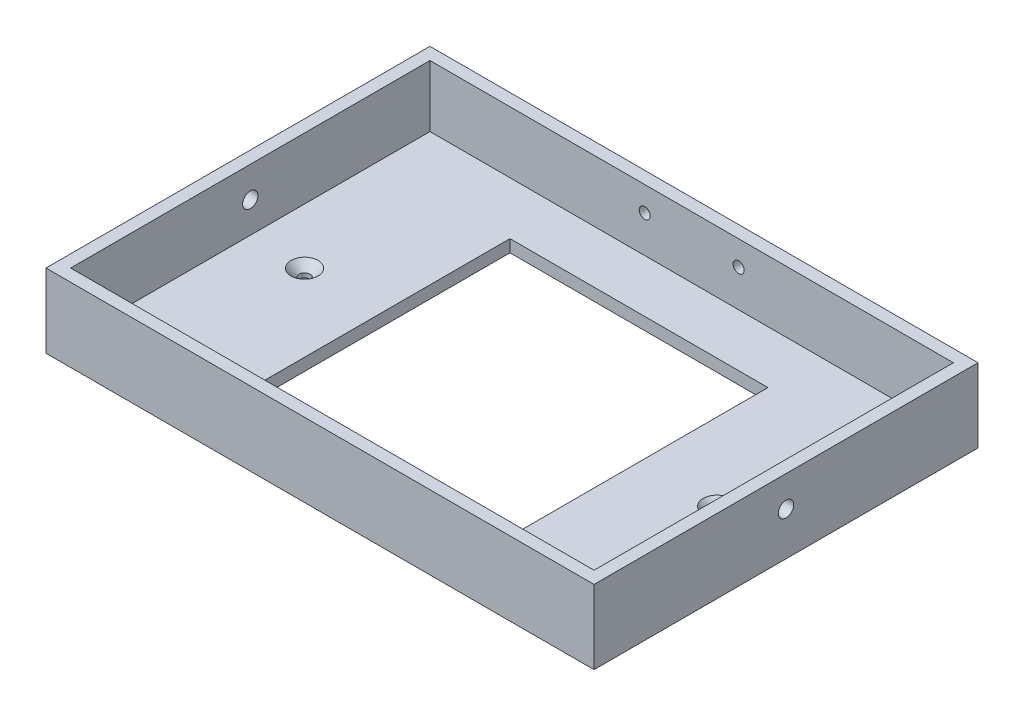
SolidWorks part; units mm, degrees
material "[PLA] Orange"
ref_plane "Front Plane" through (0, 0, 0) normal (0, 0, 1) x (1, 0, 0)
ref_plane "Top Plane" through (0, 0, 0) normal (0, 1, 0) x (1, 0, 0)
ref_plane "Right Plane" through (0, 0, 0) normal (1, 0, 0) x (0, 0, -1)
sketch "Sketch1" plane through (0, 0, 0) normal (0, 1, 0) x (1, 0, 0)
  line L0 (-44.545, -31.21) -> (-44.545, 31.21)
  line L1 (-42.545, -29.21) -> (42.545, -29.21)
  line L2 (-42.545, -29.21) -> (-42.545, 29.21)
  line L3 (-42.545, 29.21) -> (42.545, 29.21)
  line L4 (42.545, -29.21) -> (42.545, 29.21)
  line L5 (-42.545, -29.21) -> (42.545, 29.21) construction
  line L6 (-42.545, 29.21) -> (42.545, -29.21) construction
  line L7 (-44.545, 31.21) -> (44.545, 31.21)
  line L8 (44.545, -31.21) -> (44.545, 31.21)
  line L9 (-44.545, -31.21) -> (44.545, -31.21)
  point P0 (0, 0)
  dimension "D1" = 58.42
  dimension "D2" = 85.09
  dimension "D3" = 2
extrude "Boss-Extrude1" add sketch "Sketch1" against normal blind 2 contours L1 L4 L3 L2 | L0 L9 L8 L7 L4 L1 L2 L3 region at (-43.4572, 0, 0) region at (0, 0, 0)
extrude "Boss-Extrude2" add sketch "Sketch1<3>" along normal blind 10
sketch "Sketch1<3>" plane through (0, 0, 0) normal (0, 1, 0) x (1, 0, 0) same geometry as "Sketch1"
hole_wizard "CSK for M2 Flat Head Machine Screw1" positions "Sketch4" profile "Sketch6" countersink size "M2" standard "ANSI Metric"
sketch "Sketch4" plane through (0, 0, 0) normal (0, 1, 0) x (1, 0, 0)
  circle A0 centre (-33.5, -0.2189) radius 0.8 construction
  circle A1 centre (33.5, -0.2189) radius 0.8 construction
  point P156 (-33.5, -0.2189)
  point P158 (33.5, -0.2189)
sketch "Sketch6" plane through (-33.5, 0, 0.2189) normal (1, 0, 0) x (0, 0, 1)
  line L0 (0, 0) -> (0, 10.4468)
  line L1 (0, 10.4468) -> (0.9, 9.906)
  line L2 (0.9, 9.906) -> (0.9, 1.3)
  line L3 (0.9, 1.3) -> (2.2, 0)
  line L5 (2.2, 0) -> (0, 0)
  line L6 (-0.9, 1.3) -> (-2.2, 0) construction
  line L10 (0, 10.4468) -> (-0.9, 9.906) construction
  line L11 (0, -6.35) -> (0, 107.95) construction
  dimension "Hole Dia." = 1.8
  dimension "Hole Depth" = 9.906
  dimension "Near C'Sink Dia." = 4.4
  dimension "Near C'Sink Angle" = 90
  dimension "Drill Angle" = 118
sketch "Sketch7" plane through (0, 0, 0) normal (0, 1, 0) x (1, 0, 0)
  line L1 (-20.9676, -20.6397) -> (20.9676, -20.6397)
  line L2 (-20.9676, -20.6397) -> (-20.9676, 20.6397)
  line L3 (-20.9676, 20.6397) -> (20.9676, 20.6397)
  line L4 (20.9676, -20.6397) -> (20.9676, 20.6397)
  line L5 (-20.9676, -20.6397) -> (20.9676, 20.6397) construction
  line L6 (-20.9676, 20.6397) -> (20.9676, -20.6397) construction
  point P0 (0, 0)
extrude "Cut-Extrude1" cut sketch "Sketch7" against normal blind 2.54
sketch "Sketch8" plane through (0, 0, -31.21) normal (0, 0, -1) x (-1, 0, 0)
  line L0 (-7.635, 6) -> (7.635, 6) construction
  line L1 (0, 6) -> (0, 0) construction
  line L2 (-44.545, 10) -> (44.545, 10) construction
  circle A0 centre (-7.635, 6) radius 0.9
  circle A1 centre (7.635, 6) radius 0.9
  dimension "D1" = 1.8
  dimension "D2" = 15.27
  dimension "D3" = 4
extrude "Cut-Extrude2" cut sketch "Sketch8" against normal up to next
sketch "Sketch9" plane through (44.545, 0, 0) normal (1, 0, 0) x (0, 0, -1)
  line L0 (-31.21, 5) -> (31.21, 5) construction
  line L1 (-31.21, -2) -> (-31.21, 10) construction
  line L2 (31.21, -2) -> (31.21, 10) construction
  line L3 (29.21, 0) -> (-29.21, 0) construction
  line L4 (-31.21, 10) -> (31.21, 10) construction
  line L5 (0, 10) -> (0, -2) construction
  line L6 (-31.21, -2) -> (31.21, -2) construction
  circle A0 centre (0, 5) radius 1.25
  dimension "D1" = 2.5
  dimension "D2" = 5
extrude "Cut-Extrude3" cut sketch "Sketch9" against normal through all
